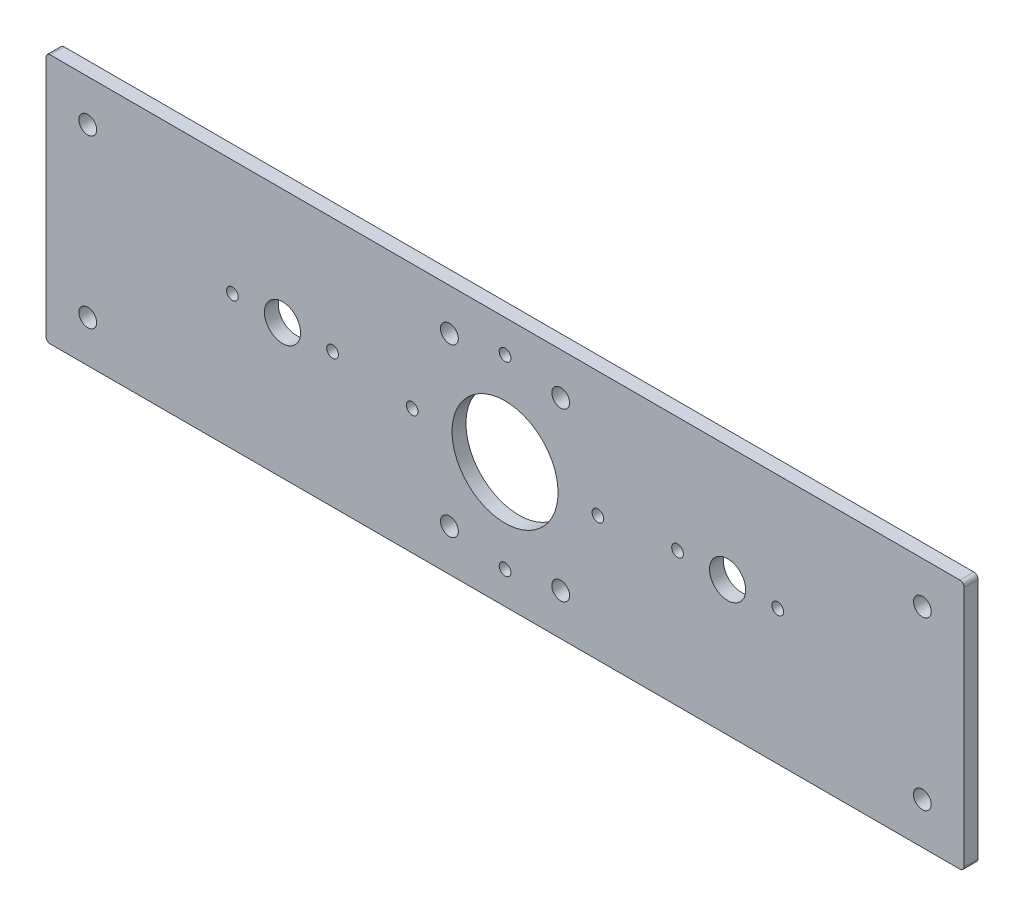
SolidWorks part; units mm, degrees
ref_plane "Front Plane" through (0, 0, 0) normal (0, 0, 1) x (1, 0, 0)
ref_plane "Top Plane" through (0, 0, 0) normal (0, 1, 0) x (1, 0, 0)
ref_plane "Right Plane" through (0, 0, 0) normal (1, 0, 0) x (0, 0, -1)
sketch "Sketch1" plane through (0, 0, 0) normal (0, 0, 1) x (1, 0, 0)
  line L1 (165, -45) -> (-165, -45)
  line L2 (165, -45) -> (165, 45)
  line L3 (165, 45) -> (-165, 45)
  line L4 (-165, -45) -> (-165, 45)
  line L5 (165, -45) -> (-165, 45) construction
  line L6 (165, 45) -> (-165, -45) construction
  circle A0 centre (0, 0) radius 19.05
  point P0 (0, 0)
  dimension "D3" = 38.1
  dimension "D1" = 90
  dimension "D2" = 330
extrude "Boss-Extrude1" add sketch "Sketch1" along normal mid plane 5
hole_wizard "M6 Clearance Hole1" positions "Sketch5" profile "Sketch4" hole size "M6" standard "ANSI Metric" end condition through all
sketch "Sketch5" plane through (0, 0, 2.5) normal (0, 0, 1) x (1, 0, 0)
  line L0 (165, 45) -> (-165, 45) construction
  line L1 (-165, 45) -> (-165, -45) construction
  line L2 (-165, -45) -> (165, -45) construction
  point P0 (-150, 30)
  point P2 (-20, 30)
  point P4 (-20, -30)
  point P6 (-150, -30)
  dimension "D1" = 15
  dimension "D2" = 20
  dimension "D3" = 15
  dimension "D4" = 15
  dimension "D5" = 15
  dimension "D6" = 15
  dimension "D7" = 15
  dimension "D8" = 20
sketch "Sketch4" plane through (-150, 30, 2.5) normal (1, 0, 0) x (0, -1, 0)
  line L0 (0, 0) -> (0, 5)
  line L1 (0, 5) -> (3.2, 5)
  line L2 (3.2, 5) -> (3.2, 0)
  line L5 (3.2, 0) -> (0, 0)
  line L11 (0, -6.35) -> (0, 107.95) construction
  dimension "Thru Hole Dia." = 6.4
  dimension "Thru Hole Depth" = 5
mirror "Mirror2" about plane through (0, 0, 0) normal (1, 0, 0) of "M6 Clearance Hole1"
sketch "Sketch3" plane through (0, 0, 2.5) normal (0, 0, 1) x (1, 0, 0)
  line L0 (0, 3.4) -> (-49.4534, 3.4) construction
  circle A2 centre (-80, 3.4) radius 6.5
  dimension "D3" = 13
  dimension "D4" = 80
  dimension "D7" = 3.4
extrude "Cut-Extrude2" cut sketch "Sketch3" against normal through all
hole_wizard "M5x0.8 Tapped Hole1" positions "Sketch7" profile "Sketch6" tap size "M5x0.8" standard "ANSI Metric" end condition through all
sketch "Sketch7" plane through (0, 0, 2.5) normal (0, 0, 1) x (1, 0, 0)
  line L0 (-1080, 3.4) -> (48920, 3.4) construction
  circle A0 centre (-80, 3.4) radius 6.5 construction
  point P0 (-98, 3.4)
  point P2 (-62, 3.4)
  dimension "D1" = 18
  dimension "D2" = 18
sketch "Sketch6" plane through (-98, 3.4, 2.5) normal (1, 0, 0) x (0, -1, 0)
  line L0 (0, 0) -> (0, 5)
  line L1 (0, 5) -> (2.1, 5)
  line L2 (2.1, 5) -> (2.1, 0)
  line L5 (2.1, 0) -> (0, 0)
  line L11 (0, -6.35) -> (0, 107.95) construction
  dimension "Thru Tap Drill Dia." = 4.2
  dimension "Thru Tap Drill Depth" = 5
cosmetic thread "Hole Thread1" parameters "D2"=5
cosmetic thread "Hole Thread2" parameters "D2"=5
mirror "Mirror1" about plane through (0, 0, 0) normal (1, 0, 0) of "M5x0.8 Tapped Hole1", "Cut-Extrude2"
hole_wizard "M5x0.8 Tapped Hole3" positions "Sketch9" profile "Sketch8" tap size "M5x0.8" standard "ANSI Metric" end condition through all
sketch "Sketch9" plane through (0, 0, 2.5) normal (0, 0, 1) x (1, 0, 0)
  line L1 (0, -33.3754) -> (33.3754, 0) construction
  line L2 (0, -33.3754) -> (-33.3754, 0) construction
  line L3 (-33.3754, 0) -> (0, 33.3754) construction
  line L4 (33.3754, 0) -> (0, 33.3754) construction
  line L5 (0, -33.3754) -> (0, 33.3754) construction
  line L6 (-33.3754, 0) -> (33.3754, 0) construction
  line L7 (-1000, 0) -> (49000, 0) construction
  point P1 (0, 33.3754)
  point P164 (0, -33.3754)
  point P165 (-33.3754, 0)
  point P166 (33.3754, 0)
  dimension "D1" = 47.2
  dimension "D2" = 47.2
  dimension "D3" = 90
  dimension "D4" = 90
  dimension "D5" = 90
  dimension "D6" = 90
  dimension "D7" = 23.6
  dimension "D8" = 23.6
sketch "Sketch8" plane through (0, 33.3754, 2.5) normal (1, 0, 0) x (0, -1, 0)
  line L0 (0, 0) -> (0, 5)
  line L1 (0, 5) -> (2.1, 5)
  line L2 (2.1, 5) -> (2.1, 0)
  line L5 (2.1, 0) -> (0, 0)
  line L11 (0, -6.35) -> (0, 107.95) construction
  dimension "Thru Tap Drill Dia." = 4.2
  dimension "Thru Tap Drill Depth" = 5
cosmetic thread "Hole Thread3" parameters "D2"=5
cosmetic thread "Hole Thread4" parameters "D2"=5
cosmetic thread "Hole Thread5" parameters "D2"=5
cosmetic thread "Hole Thread6" parameters "D2"=5
fillet "Fillet1" radius 1.5 4 edges at (-165, -45, 0) (165, -45, 0) (165, 45, 0) (-165, 45, 0)
equation "\"D4@Sketch3\"=160/2"
